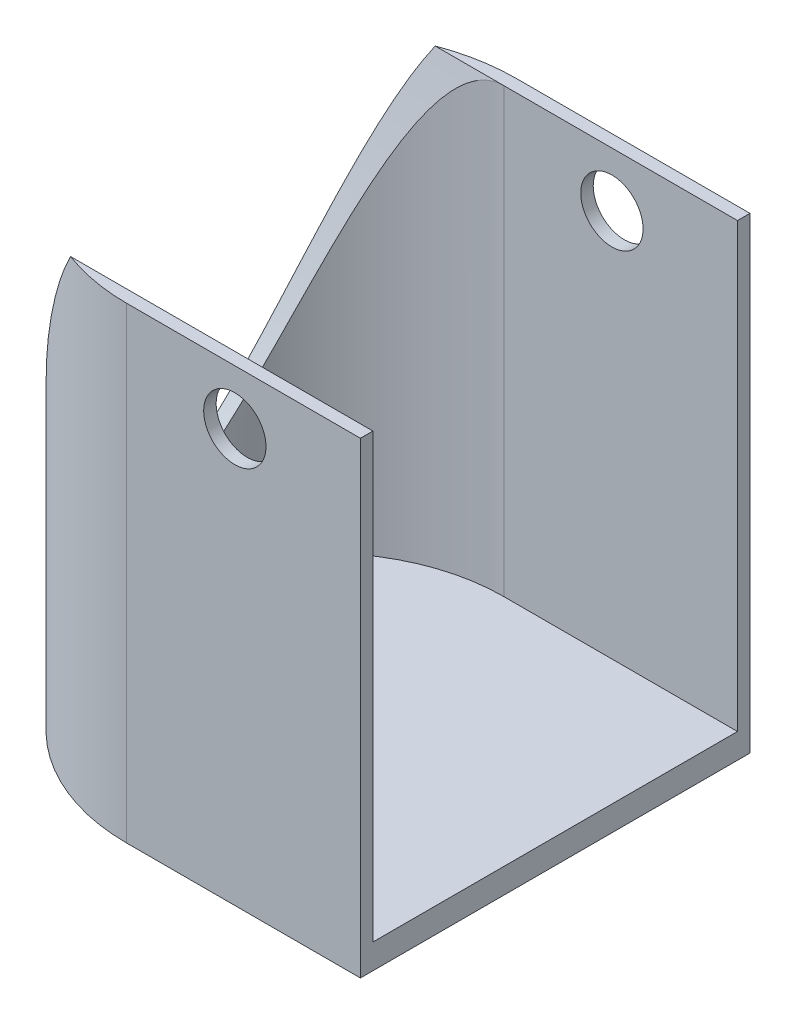
SolidWorks part; units mm, degrees
ref_plane "Front Plane" through (0, 0, 0) normal (0, 0, 1) x (1, 0, 0)
ref_plane "Top Plane" through (0, 0, 0) normal (0, 1, 0) x (1, 0, 0)
ref_plane "Right Plane" through (0, 0, 0) normal (1, 0, 0) x (0, 0, -1)
sketch "Sketch1" plane through (0, 0, 0) normal (0, 1, 0) x (1, 0, 0)
  line L0 (0, 11.7) -> (13.4, 11.7)
  line L2 (13.4, -11.7) -> (0, -11.7)
  line L3 (0, 12.5) -> (15, 12.5)
  line L4 (15, 12.5) -> (15, -12.5)
  line L5 (15, -12.5) -> (0, -12.5)
  line L6 (13.4, 11.7) -> (15, 11.7)
  line L7 (13.4, -11.7) -> (15, -11.7)
  arc A0 (0, 12.5) -> (0, -12.5) centre (0, 0) ccw
  circle A1 centre (0, 0) radius 11.7
  dimension "D1" = 25
  dimension "D2" = 23.4
  dimension "D3" = 13.4
extrude "Boss-Extrude2" add sketch "Sketch1" along normal blind 30 contours A1 L0 L6 L4 L3 A0 L5 L7 L2 region at (-12.0717, 0, 0)
extrude "Boss-Extrude3" add sketch "Sketch1<5>" along normal blind 1.6 contours A1 L2 L7 L4 L6 L0 | A1 region at (6.7, 0, -11.4221) region at (0, 0, 0)
sketch "Sketch1<5>" plane through (0, 0, 0) normal (0, 1, 0) x (1, 0, 0) same geometry as "Sketch1"
sketch "Sketch3" plane through (0, 0, 0) normal (1, 0, 0) x (0, 0, -1)
  line L0 (-11.7, 30) -> (11.7, 30)
  spline S0 degree 2 poles (-11.7, 30) (0, -19.4139) (11.7, 30) knots 0 0 0 1 1 1
extrude "Cut-Extrude2" cut sketch "Sketch3" against normal up to next
sketch "Sketch4" plane through (0, 0, 0) normal (0, -1, 0) x (1, 0, 0)
  circle A0 centre (0, 0) radius 2
  dimension "D1" = 4
extrude "Cut-Extrude3" cut sketch "Sketch4" against normal up to next
sketch "Sketch5" plane through (0, 0, -12.5) normal (0, 0, -1) x (-1, 0, 0)
  circle A0 centre (-6.941, 26.5006) radius 2
  dimension "D1" = 4
extrude "Cut-Extrude4" cut sketch "Sketch5" along direction (0, 0, -1) on the side against the normal through all and the other way through all
